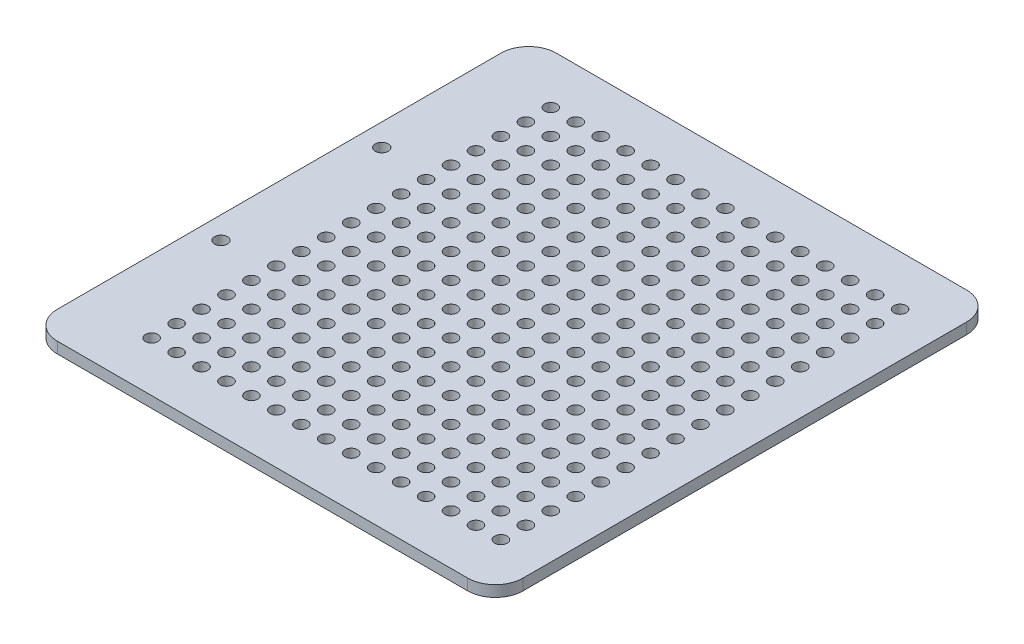
SolidWorks part; units mm, degrees
ref_plane "前视基准面" through (0, 0, 0) normal (0, 0, 1) x (1, 0, 0)
ref_plane "上视基准面" through (0, 0, 0) normal (0, 1, 0) x (1, 0, 0)
ref_plane "右视基准面" through (0, 0, 0) normal (1, 0, 0) x (0, 0, -1)
other "Configuration Table"
sketch "草图1" plane through (0, 0, 0) normal (0, 1, 0) x (1, 0, 0)
  line L1 (0, 0) -> (168, 0)
  line L2 (0, 0) -> (0, -180)
  line L3 (0, -180) -> (168, -180)
  line L4 (168, 0) -> (168, -180)
  dimension "D1" = 180
  dimension "D2" = 168
extrude "凸台-拉伸1" add sketch "草图1" along normal blind 4
sketch "草图3" plane through (0, 4, 0) normal (0, 1, 0) x (1, 0, 0)
  line L0 (0, -90) -> (18.8145, -90) construction
  line L1 (0, 0) -> (0, -180) construction
  line L2 (8, -61) -> (8, -119) construction
  circle A0 centre (8, -61) radius 2.3366
  circle A1 centre (8, -119) radius 2.3366
  dimension "D1" = 58
  dimension "D2" = 8
extrude "切除-拉伸1" cut sketch "草图3" against normal blind 4
sketch "草图5" plane through (0, 4, 0) normal (0, 1, 0) x (1, 0, 0)
  line L0 (168, 0) -> (0, 0) construction
  line L2 (0, 0) -> (0, -180) construction
  circle A0 centre (26, -18) radius 2.25
  circle A1 centre (35, -18) radius 2.25
  circle A2 centre (44, -18) radius 2.25
  circle A3 centre (53, -18) radius 2.25
  circle A4 centre (62, -18) radius 2.25
  circle A5 centre (71, -18) radius 2.25
  circle A6 centre (80, -18) radius 2.25
  circle A7 centre (89, -18) radius 2.25
  circle A8 centre (98, -18) radius 2.25
  circle A9 centre (107, -18) radius 2.25
  circle A10 centre (116, -18) radius 2.25
  circle A11 centre (125, -18) radius 2.25
  circle A12 centre (134, -18) radius 2.25
  circle A13 centre (143, -18) radius 2.25
  circle A14 centre (152, -18) radius 2.25
  circle A15 centre (35, -27) radius 2.25
  circle A16 centre (44, -27) radius 2.25
  circle A17 centre (53, -27) radius 2.25
  circle A18 centre (62, -27) radius 2.25
  circle A19 centre (71, -27) radius 2.25
  circle A20 centre (80, -27) radius 2.25
  circle A21 centre (89, -27) radius 2.25
  circle A22 centre (98, -27) radius 2.25
  circle A23 centre (107, -27) radius 2.25
  circle A24 centre (116, -27) radius 2.25
  circle A25 centre (125, -27) radius 2.25
  circle A26 centre (134, -27) radius 2.25
  circle A27 centre (143, -27) radius 2.25
  circle A28 centre (152, -27) radius 2.25
  circle A29 centre (35, -36) radius 2.25
  circle A30 centre (44, -36) radius 2.25
  circle A31 centre (53, -36) radius 2.25
  circle A32 centre (62, -36) radius 2.25
  circle A33 centre (71, -36) radius 2.25
  circle A34 centre (80, -36) radius 2.25
  circle A35 centre (89, -36) radius 2.25
  circle A36 centre (98, -36) radius 2.25
  circle A37 centre (107, -36) radius 2.25
  circle A38 centre (116, -36) radius 2.25
  circle A39 centre (125, -36) radius 2.25
  circle A40 centre (134, -36) radius 2.25
  circle A41 centre (143, -36) radius 2.25
  circle A42 centre (152, -36) radius 2.25
  circle A43 centre (35, -45) radius 2.25
  circle A44 centre (44, -45) radius 2.25
  circle A45 centre (53, -45) radius 2.25
  circle A46 centre (62, -45) radius 2.25
  circle A47 centre (71, -45) radius 2.25
  circle A48 centre (80, -45) radius 2.25
  circle A49 centre (89, -45) radius 2.25
  circle A50 centre (98, -45) radius 2.25
  circle A51 centre (107, -45) radius 2.25
  circle A52 centre (116, -45) radius 2.25
  circle A53 centre (125, -45) radius 2.25
  circle A54 centre (134, -45) radius 2.25
  circle A55 centre (143, -45) radius 2.25
  circle A56 centre (152, -45) radius 2.25
  circle A57 centre (35, -54) radius 2.25
  circle A58 centre (44, -54) radius 2.25
  circle A59 centre (53, -54) radius 2.25
  circle A60 centre (62, -54) radius 2.25
  circle A61 centre (71, -54) radius 2.25
  circle A62 centre (80, -54) radius 2.25
  circle A63 centre (89, -54) radius 2.25
  circle A64 centre (98, -54) radius 2.25
  circle A65 centre (107, -54) radius 2.25
  circle A66 centre (116, -54) radius 2.25
  circle A67 centre (125, -54) radius 2.25
  circle A68 centre (134, -54) radius 2.25
  circle A69 centre (143, -54) radius 2.25
  circle A70 centre (152, -54) radius 2.25
  circle A71 centre (35, -63) radius 2.25
  circle A72 centre (44, -63) radius 2.25
  circle A73 centre (53, -63) radius 2.25
  circle A74 centre (62, -63) radius 2.25
  circle A75 centre (71, -63) radius 2.25
  circle A76 centre (80, -63) radius 2.25
  circle A77 centre (89, -63) radius 2.25
  circle A78 centre (98, -63) radius 2.25
  circle A79 centre (107, -63) radius 2.25
  circle A80 centre (116, -63) radius 2.25
  circle A81 centre (125, -63) radius 2.25
  circle A82 centre (134, -63) radius 2.25
  circle A83 centre (143, -63) radius 2.25
  circle A84 centre (152, -63) radius 2.25
  circle A85 centre (35, -72) radius 2.25
  circle A86 centre (44, -72) radius 2.25
  circle A87 centre (53, -72) radius 2.25
  circle A88 centre (62, -72) radius 2.25
  circle A89 centre (71, -72) radius 2.25
  circle A90 centre (80, -72) radius 2.25
  circle A91 centre (89, -72) radius 2.25
  circle A92 centre (98, -72) radius 2.25
  circle A93 centre (107, -72) radius 2.25
  circle A94 centre (116, -72) radius 2.25
  circle A95 centre (125, -72) radius 2.25
  circle A96 centre (134, -72) radius 2.25
  circle A97 centre (143, -72) radius 2.25
  circle A98 centre (152, -72) radius 2.25
  circle A99 centre (35, -81) radius 2.25
  circle A100 centre (44, -81) radius 2.25
  circle A101 centre (53, -81) radius 2.25
  circle A102 centre (62, -81) radius 2.25
  circle A103 centre (71, -81) radius 2.25
  circle A104 centre (80, -81) radius 2.25
  circle A105 centre (89, -81) radius 2.25
  circle A106 centre (98, -81) radius 2.25
  circle A107 centre (107, -81) radius 2.25
  circle A108 centre (116, -81) radius 2.25
  circle A109 centre (125, -81) radius 2.25
  circle A110 centre (134, -81) radius 2.25
  circle A111 centre (143, -81) radius 2.25
  circle A112 centre (152, -81) radius 2.25
  circle A113 centre (35, -90) radius 2.25
  circle A114 centre (44, -90) radius 2.25
  circle A115 centre (53, -90) radius 2.25
  circle A116 centre (62, -90) radius 2.25
  circle A117 centre (71, -90) radius 2.25
  circle A118 centre (80, -90) radius 2.25
  circle A119 centre (89, -90) radius 2.25
  circle A120 centre (98, -90) radius 2.25
  circle A121 centre (107, -90) radius 2.25
  circle A122 centre (116, -90) radius 2.25
  circle A123 centre (125, -90) radius 2.25
  circle A124 centre (134, -90) radius 2.25
  circle A125 centre (143, -90) radius 2.25
  circle A126 centre (152, -90) radius 2.25
  circle A127 centre (35, -99) radius 2.25
  circle A128 centre (44, -99) radius 2.25
  circle A129 centre (53, -99) radius 2.25
  circle A130 centre (62, -99) radius 2.25
  circle A131 centre (71, -99) radius 2.25
  circle A132 centre (80, -99) radius 2.25
  circle A133 centre (89, -99) radius 2.25
  circle A134 centre (98, -99) radius 2.25
  circle A135 centre (107, -99) radius 2.25
  circle A136 centre (116, -99) radius 2.25
  circle A137 centre (125, -99) radius 2.25
  circle A138 centre (134, -99) radius 2.25
  circle A139 centre (143, -99) radius 2.25
  circle A140 centre (152, -99) radius 2.25
  circle A141 centre (35, -108) radius 2.25
  circle A142 centre (44, -108) radius 2.25
  circle A143 centre (53, -108) radius 2.25
  circle A144 centre (62, -108) radius 2.25
  circle A145 centre (71, -108) radius 2.25
  circle A146 centre (80, -108) radius 2.25
  circle A147 centre (89, -108) radius 2.25
  circle A148 centre (98, -108) radius 2.25
  circle A149 centre (107, -108) radius 2.25
  circle A150 centre (116, -108) radius 2.25
  circle A151 centre (125, -108) radius 2.25
  circle A152 centre (134, -108) radius 2.25
  circle A153 centre (143, -108) radius 2.25
  circle A154 centre (152, -108) radius 2.25
  circle A155 centre (35, -117) radius 2.25
  circle A156 centre (44, -117) radius 2.25
  circle A157 centre (53, -117) radius 2.25
  circle A158 centre (62, -117) radius 2.25
  circle A159 centre (71, -117) radius 2.25
  circle A160 centre (80, -117) radius 2.25
  circle A161 centre (89, -117) radius 2.25
  circle A162 centre (98, -117) radius 2.25
  circle A163 centre (107, -117) radius 2.25
  circle A164 centre (116, -117) radius 2.25
  circle A165 centre (125, -117) radius 2.25
  circle A166 centre (134, -117) radius 2.25
  circle A167 centre (143, -117) radius 2.25
  circle A168 centre (152, -117) radius 2.25
  circle A169 centre (35, -126) radius 2.25
  circle A170 centre (44, -126) radius 2.25
  circle A171 centre (53, -126) radius 2.25
  circle A172 centre (62, -126) radius 2.25
  circle A173 centre (71, -126) radius 2.25
  circle A174 centre (80, -126) radius 2.25
  circle A175 centre (89, -126) radius 2.25
  circle A176 centre (98, -126) radius 2.25
  circle A177 centre (107, -126) radius 2.25
  circle A178 centre (116, -126) radius 2.25
  circle A179 centre (125, -126) radius 2.25
  circle A180 centre (134, -126) radius 2.25
  circle A181 centre (143, -126) radius 2.25
  circle A182 centre (152, -126) radius 2.25
  circle A183 centre (35, -135) radius 2.25
  circle A184 centre (44, -135) radius 2.25
  circle A185 centre (53, -135) radius 2.25
  circle A186 centre (62, -135) radius 2.25
  circle A187 centre (71, -135) radius 2.25
  circle A188 centre (80, -135) radius 2.25
  circle A189 centre (89, -135) radius 2.25
  circle A190 centre (98, -135) radius 2.25
  circle A191 centre (107, -135) radius 2.25
  circle A192 centre (116, -135) radius 2.25
  circle A193 centre (125, -135) radius 2.25
  circle A194 centre (134, -135) radius 2.25
  circle A195 centre (143, -135) radius 2.25
  circle A196 centre (152, -135) radius 2.25
  circle A197 centre (35, -144) radius 2.25
  circle A198 centre (44, -144) radius 2.25
  circle A199 centre (53, -144) radius 2.25
  circle A200 centre (62, -144) radius 2.25
  circle A201 centre (71, -144) radius 2.25
  circle A202 centre (80, -144) radius 2.25
  circle A203 centre (89, -144) radius 2.25
  circle A204 centre (98, -144) radius 2.25
  circle A205 centre (107, -144) radius 2.25
  circle A206 centre (116, -144) radius 2.25
  circle A207 centre (125, -144) radius 2.25
  circle A208 centre (134, -144) radius 2.25
  circle A209 centre (143, -144) radius 2.25
  circle A210 centre (152, -144) radius 2.25
  circle A211 centre (35, -153) radius 2.25
  circle A212 centre (44, -153) radius 2.25
  circle A213 centre (53, -153) radius 2.25
  circle A214 centre (62, -153) radius 2.25
  circle A215 centre (71, -153) radius 2.25
  circle A216 centre (80, -153) radius 2.25
  circle A217 centre (89, -153) radius 2.25
  circle A218 centre (98, -153) radius 2.25
  circle A219 centre (107, -153) radius 2.25
  circle A220 centre (116, -153) radius 2.25
  circle A221 centre (125, -153) radius 2.25
  circle A222 centre (134, -153) radius 2.25
  circle A223 centre (143, -153) radius 2.25
  circle A224 centre (152, -153) radius 2.25
  circle A225 centre (35, -162) radius 2.25
  circle A226 centre (44, -162) radius 2.25
  circle A227 centre (53, -162) radius 2.25
  circle A228 centre (62, -162) radius 2.25
  circle A229 centre (71, -162) radius 2.25
  circle A230 centre (80, -162) radius 2.25
  circle A231 centre (89, -162) radius 2.25
  circle A232 centre (98, -162) radius 2.25
  circle A233 centre (107, -162) radius 2.25
  circle A234 centre (116, -162) radius 2.25
  circle A235 centre (125, -162) radius 2.25
  circle A236 centre (134, -162) radius 2.25
  circle A237 centre (143, -162) radius 2.25
  circle A238 centre (152, -162) radius 2.25
  circle A239 centre (26, -27) radius 2.25
  circle A240 centre (26, -36) radius 2.25
  circle A241 centre (26, -45) radius 2.25
  circle A242 centre (26, -54) radius 2.25
  circle A243 centre (26, -63) radius 2.25
  circle A244 centre (26, -72) radius 2.25
  circle A245 centre (26, -81) radius 2.25
  circle A246 centre (26, -90) radius 2.25
  circle A247 centre (26, -99) radius 2.25
  circle A248 centre (26, -108) radius 2.25
  circle A249 centre (26, -117) radius 2.25
  circle A250 centre (26, -126) radius 2.25
  circle A251 centre (26, -135) radius 2.25
  circle A252 centre (26, -144) radius 2.25
  circle A253 centre (26, -153) radius 2.25
  circle A254 centre (26, -162) radius 2.25
  dimension "D2" = 26
  dimension "D5" = 4.5
  dimension "D1" = 18
  dimension "D3" = 15
  dimension "D4" = 17
extrude "切除-拉伸2" cut sketch "草图5" against normal blind 4
fillet "圆角1" radius 10 4 edges at (0, 2, 180) (168, 2, 180) (168, 2, 0) (0, 2, 0)
